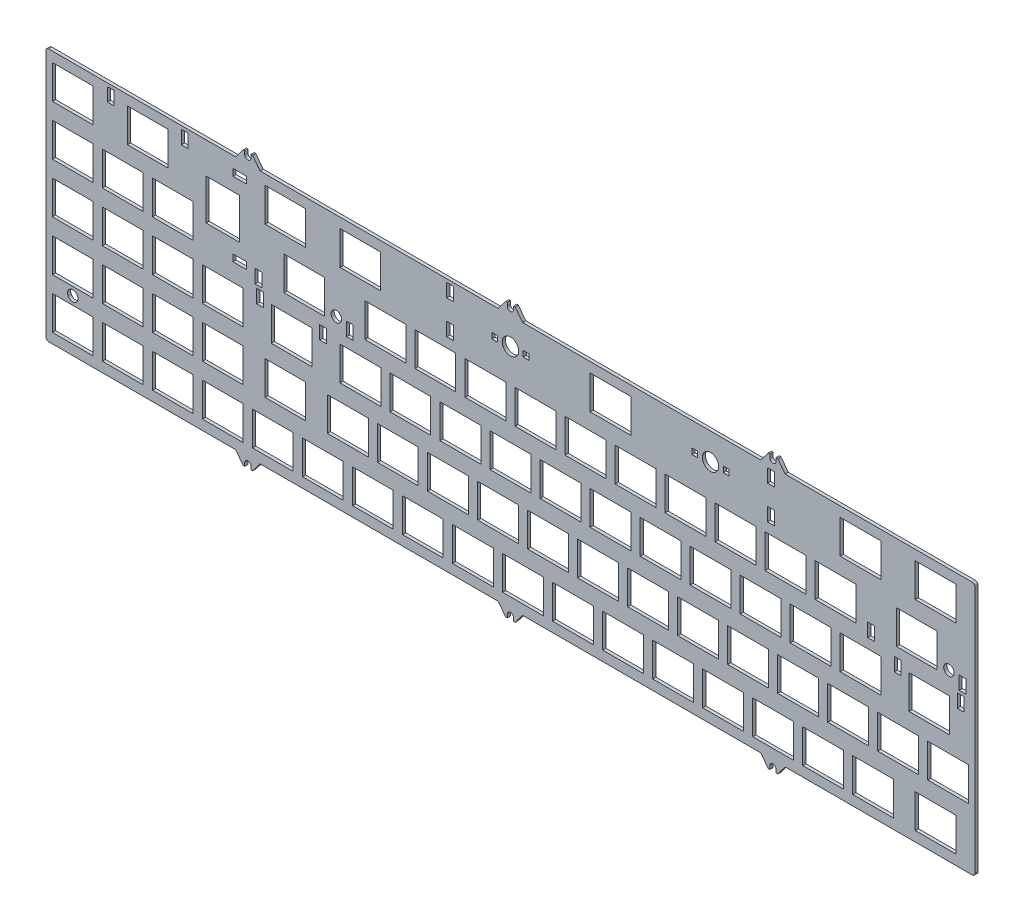
SolidWorks part; units mm, degrees
ref_plane "Front Plane" through (0, 0, 0) normal (0, 0, 1) x (1, 0, 0)
ref_plane "Top Plane" through (0, 0, 0) normal (0, 1, 0) x (1, 0, 0)
ref_plane "Right Plane" through (0, 0, 0) normal (1, 0, 0) x (0, 0, -1)
sketch "Sketch2" plane through (0, 0, 0) normal (0, 0, -1) x (1, 0, 0)
  line L0 (137.0625, 39.4) -> (121.4625, 39.4)
  line L1 (121.4625, 39.4) -> (121.4625, 26.6)
  line L2 (121.4625, 26.6) -> (137.0625, 26.6)
  line L3 (137.0625, 26.6) -> (137.0625, 39.4)
  line L4 (127.5375, 58.45) -> (111.9375, 58.45)
  line L5 (111.9375, 58.45) -> (111.9375, 45.65)
  line L6 (111.9375, 45.65) -> (127.5375, 45.65)
  line L7 (127.5375, 45.65) -> (127.5375, 58.45)
  line L8 (122.775, 77.5) -> (107.175, 77.5)
  line L9 (107.175, 77.5) -> (107.175, 64.7)
  line L10 (107.175, 64.7) -> (122.775, 64.7)
  line L11 (122.775, 64.7) -> (122.775, 77.5)
  line L12 (325.7312, 43.1) -> (325.7312, 48.2)
  line L13 (325.7312, 48.2) -> (323.1312, 48.2)
  line L14 (323.1312, 48.2) -> (323.1312, 43.1)
  line L15 (323.1312, 43.1) -> (325.7312, 43.1)
  line L16 (347.1312, 43.1) -> (347.1312, 48.2)
  line L17 (347.1312, 48.2) -> (349.7312, 48.2)
  line L18 (349.7312, 48.2) -> (349.7312, 43.1)
  line L19 (349.7312, 43.1) -> (347.1312, 43.1)
  line L20 (104.2437, 43.1) -> (104.2437, 48.2)
  line L21 (104.2437, 48.2) -> (106.8437, 48.2)
  line L22 (106.8437, 48.2) -> (106.8437, 43.1)
  line L23 (106.8437, 43.1) -> (104.2437, 43.1)
  line L24 (315.5687, 36.85) -> (315.5687, 41.95)
  line L25 (315.5687, 41.95) -> (312.9687, 41.95)
  line L26 (312.9687, 41.95) -> (312.9687, 36.85)
  line L27 (312.9687, 36.85) -> (315.5687, 36.85)
  line L28 (347.7687, 36.85) -> (347.7687, 41.95)
  line L29 (347.7687, 41.95) -> (350.3687, 41.95)
  line L30 (350.3687, 41.95) -> (350.3687, 36.85)
  line L31 (350.3687, 36.85) -> (347.7687, 36.85)
  line L32 (114.4062, 36.85) -> (114.4062, 41.95)
  line L33 (114.4062, 41.95) -> (117.0062, 41.95)
  line L34 (117.0062, 41.95) -> (117.0062, 36.85)
  line L35 (117.0062, 36.85) -> (114.4062, 36.85)
  line L36 (155.1875, 5) -> (155.1875, 10.1)
  line L37 (155.1875, 10.1) -> (152.5875, 10.1)
  line L38 (152.5875, 10.1) -> (152.5875, 5)
  line L39 (152.5875, 5) -> (155.1875, 5)
  line L40 (183.9625, 15.05) -> (183.9625, 12.85)
  line L41 (183.9625, 12.85) -> (181.7625, 12.85)
  line L42 (181.7625, 12.85) -> (181.7625, 15.05)
  line L43 (181.7625, 15.05) -> (183.9625, 15.05)
  line L44 (169.8125, 12.85) -> (169.8125, 15.05)
  line L45 (169.8125, 15.05) -> (172.0125, 15.05)
  line L46 (172.0125, 15.05) -> (172.0125, 12.85)
  line L47 (172.0125, 12.85) -> (169.8125, 12.85)
  line L48 (246.0125, 15.05) -> (246.0125, 12.85)
  line L49 (246.0125, 12.85) -> (248.2125, 12.85)
  line L50 (248.2125, 12.85) -> (248.2125, 15.05)
  line L51 (248.2125, 15.05) -> (246.0125, 15.05)
  line L52 (260.1625, 12.85) -> (260.1625, 15.05)
  line L53 (260.1625, 15.05) -> (257.9625, 15.05)
  line L54 (257.9625, 15.05) -> (257.9625, 12.85)
  line L55 (257.9625, 12.85) -> (260.1625, 12.85)
  line L56 (82.8437, 43.1) -> (82.8437, 48.2)
  line L57 (82.8437, 48.2) -> (80.2437, 48.2)
  line L58 (80.2437, 48.2) -> (80.2437, 43.1)
  line L59 (80.2437, 43.1) -> (82.8437, 43.1)
  line L60 (82.2062, 36.85) -> (82.2062, 41.95)
  line L61 (82.2062, 41.95) -> (79.6062, 41.95)
  line L62 (79.6062, 41.95) -> (79.6062, 36.85)
  line L63 (79.6062, 36.85) -> (82.2062, 36.85)
  line L64 (25.975, 5) -> (25.975, 10.1)
  line L65 (25.975, 10.1) -> (23.375, 10.1)
  line L66 (23.375, 10.1) -> (23.375, 5)
  line L67 (23.375, 5) -> (25.975, 5)
  line L68 (51.575, 5) -> (51.575, 10.1)
  line L69 (51.575, 10.1) -> (54.175, 10.1)
  line L70 (54.175, 10.1) -> (54.175, 5)
  line L71 (54.175, 5) -> (51.575, 5)
  line L72 (76.3, 10.675) -> (71.2, 10.675)
  line L73 (71.2, 10.675) -> (71.2, 8.075)
  line L74 (71.2, 8.075) -> (76.3, 8.075)
  line L75 (76.3, 8.075) -> (76.3, 10.675)
  line L76 (76.3, 36.275) -> (71.2, 36.275)
  line L77 (71.2, 36.275) -> (71.2, 38.875)
  line L78 (71.2, 38.875) -> (76.3, 38.875)
  line L79 (76.3, 38.875) -> (76.3, 36.275)
  line L80 (155.1875, 22.9) -> (155.1875, 17.8)
  line L81 (155.1875, 17.8) -> (152.5875, 17.8)
  line L82 (152.5875, 17.8) -> (152.5875, 22.9)
  line L83 (152.5875, 22.9) -> (155.1875, 22.9)
  line L84 (277.3875, 22.9) -> (277.3875, 17.8)
  line L85 (277.3875, 17.8) -> (274.7875, 17.8)
  line L86 (274.7875, 17.8) -> (274.7875, 22.9)
  line L87 (274.7875, 22.9) -> (277.3875, 22.9)
  line L88 (274.7875, 5) -> (274.7875, 10.1)
  line L89 (274.7875, 10.1) -> (277.3875, 10.1)
  line L90 (277.3875, 10.1) -> (277.3875, 5)
  line L91 (277.3875, 5) -> (274.7875, 5)
  line L92 (0, 4.75) -> (0, 99.35)
  line L93 (353.775, 4.75) -> (353.775, 99.35)
  line L94 (75.0875, 104.1) -> (72.2375, 100.35)
  line L95 (75.0875, 104.1) -> (75.6875, 104.1)
  line L96 (75.6875, 104.1) -> (75.6875, 103.6)
  line L97 (78.6875, 104.1) -> (81.5375, 100.35)
  line L98 (78.6875, 104.1) -> (78.0875, 104.1)
  line L99 (78.0875, 104.1) -> (78.0875, 103.6)
  line L100 (175.0875, 104.1) -> (172.2375, 100.35)
  line L101 (175.0875, 104.1) -> (175.6875, 104.1)
  line L102 (178.6875, 104.1) -> (181.5375, 100.35)
  line L103 (178.6875, 104.1) -> (178.0875, 104.1)
  line L104 (275.0875, 104.1) -> (272.2375, 100.35)
  line L105 (275.0875, 104.1) -> (275.6875, 104.1)
  line L106 (278.6875, 104.1) -> (281.5375, 100.35)
  line L107 (278.6875, 104.1) -> (278.0875, 104.1)
  line L108 (272.2375, 100.35) -> (181.5375, 100.35)
  line L109 (172.2375, 100.35) -> (81.5375, 100.35)
  line L110 (72.2375, 100.35) -> (1, 100.35)
  line L111 (352.775, 100.35) -> (281.5375, 100.35)
  line L112 (272.2375, 3.75) -> (181.5375, 3.75)
  line L113 (172.2375, 3.75) -> (81.5375, 3.75)
  line L114 (72.2375, 3.75) -> (1, 3.75)
  line L115 (352.775, 3.75) -> (281.5375, 3.75)
  line L116 (331.0625, 83.75) -> (346.5625, 83.75)
  line L117 (346.5625, 83.75) -> (346.5625, 96.55)
  line L118 (346.5625, 96.55) -> (331.0625, 96.55)
  line L119 (331.0625, 96.55) -> (331.0625, 83.75)
  line L120 (307.25, 83.75) -> (322.75, 83.75)
  line L121 (322.75, 83.75) -> (322.75, 96.55)
  line L122 (322.75, 96.55) -> (307.25, 96.55)
  line L123 (307.25, 96.55) -> (307.25, 83.75)
  line L124 (288.2, 83.75) -> (303.7, 83.75)
  line L125 (303.7, 83.75) -> (303.7, 96.55)
  line L126 (303.7, 96.55) -> (288.2, 96.55)
  line L127 (288.2, 96.55) -> (288.2, 83.75)
  line L128 (269.15, 83.75) -> (284.65, 83.75)
  line L129 (284.65, 83.75) -> (284.65, 96.55)
  line L130 (284.65, 96.55) -> (269.15, 96.55)
  line L131 (269.15, 96.55) -> (269.15, 83.75)
  line L132 (250.1, 83.75) -> (265.6, 83.75)
  line L133 (265.6, 83.75) -> (265.6, 96.55)
  line L134 (265.6, 96.55) -> (250.1, 96.55)
  line L135 (250.1, 96.55) -> (250.1, 83.75)
  line L136 (231.05, 83.75) -> (246.55, 83.75)
  line L137 (246.55, 83.75) -> (246.55, 96.55)
  line L138 (246.55, 96.55) -> (231.05, 96.55)
  line L139 (231.05, 96.55) -> (231.05, 83.75)
  line L140 (212, 83.75) -> (227.5, 83.75)
  line L141 (227.5, 83.75) -> (227.5, 96.55)
  line L142 (227.5, 96.55) -> (212, 96.55)
  line L143 (212, 96.55) -> (212, 83.75)
  line L144 (192.95, 83.75) -> (208.45, 83.75)
  line L145 (208.45, 83.75) -> (208.45, 96.55)
  line L146 (208.45, 96.55) -> (192.95, 96.55)
  line L147 (192.95, 96.55) -> (192.95, 83.75)
  line L148 (173.9, 83.75) -> (189.4, 83.75)
  line L149 (189.4, 83.75) -> (189.4, 96.55)
  line L150 (189.4, 96.55) -> (173.9, 96.55)
  line L151 (173.9, 96.55) -> (173.9, 83.75)
  line L152 (154.85, 83.75) -> (170.35, 83.75)
  line L153 (170.35, 83.75) -> (170.35, 96.55)
  line L154 (170.35, 96.55) -> (154.85, 96.55)
  line L155 (154.85, 96.55) -> (154.85, 83.75)
  line L156 (135.8, 83.75) -> (151.3, 83.75)
  line L157 (151.3, 83.75) -> (151.3, 96.55)
  line L158 (151.3, 96.55) -> (135.8, 96.55)
  line L159 (135.8, 96.55) -> (135.8, 83.75)
  line L160 (116.75, 83.75) -> (132.25, 83.75)
  line L161 (132.25, 83.75) -> (132.25, 96.55)
  line L162 (132.25, 96.55) -> (116.75, 96.55)
  line L163 (116.75, 96.55) -> (116.75, 83.75)
  line L164 (97.7, 83.75) -> (113.2, 83.75)
  line L165 (113.2, 83.75) -> (113.2, 96.55)
  line L166 (113.2, 96.55) -> (97.7, 96.55)
  line L167 (97.7, 96.55) -> (97.7, 83.75)
  line L168 (78.65, 83.75) -> (94.15, 83.75)
  line L169 (94.15, 83.75) -> (94.15, 96.55)
  line L170 (94.15, 96.55) -> (78.65, 96.55)
  line L171 (78.65, 96.55) -> (78.65, 83.75)
  line L172 (59.6, 77.5) -> (75.1, 77.5)
  line L173 (75.1, 64.7) -> (75.1, 77.5)
  line L174 (75.1, 96.55) -> (59.6, 96.55)
  line L175 (59.6, 77.5) -> (59.6, 64.7)
  line L176 (40.55, 77.5) -> (56.05, 77.5)
  line L177 (56.05, 64.7) -> (56.05, 77.5)
  line L178 (56.05, 96.55) -> (40.55, 96.55)
  line L179 (40.55, 77.5) -> (40.55, 64.7)
  line L180 (21.5, 77.5) -> (37, 77.5)
  line L181 (37, 64.7) -> (37, 77.5)
  line L182 (37, 96.55) -> (21.5, 96.55)
  line L183 (21.5, 77.5) -> (21.5, 64.7)
  line L184 (2.45, 77.5) -> (17.95, 77.5)
  line L185 (17.95, 64.7) -> (17.95, 77.5)
  line L186 (17.95, 96.55) -> (2.45, 96.55)
  line L187 (2.45, 77.5) -> (2.45, 64.7)
  line L188 (59.6, 64.7) -> (75.1, 64.7)
  line L189 (75.1, 83.75) -> (75.1, 96.55)
  line L190 (75.1, 83.75) -> (59.6, 83.75)
  line L191 (59.6, 96.55) -> (59.6, 83.75)
  line L192 (40.55, 64.7) -> (56.05, 64.7)
  line L193 (56.05, 83.75) -> (56.05, 96.55)
  line L194 (56.05, 83.75) -> (40.55, 83.75)
  line L195 (40.55, 96.55) -> (40.55, 83.75)
  line L196 (21.5, 64.7) -> (37, 64.7)
  line L197 (37, 83.75) -> (37, 96.55)
  line L198 (37, 83.75) -> (21.5, 83.75)
  line L199 (21.5, 96.55) -> (21.5, 83.75)
  line L200 (2.45, 64.7) -> (17.95, 64.7)
  line L201 (17.95, 83.75) -> (17.95, 96.55)
  line L202 (17.95, 83.75) -> (2.45, 83.75)
  line L203 (2.45, 96.55) -> (2.45, 83.75)
  line L204 (59.55, 45.65) -> (75.05, 45.65)
  line L205 (75.05, 45.65) -> (75.05, 58.45)
  line L206 (75.05, 58.45) -> (59.55, 58.45)
  line L207 (59.55, 58.45) -> (59.55, 45.65)
  line L208 (40.5, 45.65) -> (56, 45.65)
  line L209 (56, 45.65) -> (56, 58.45)
  line L210 (56, 58.45) -> (40.5, 58.45)
  line L211 (40.5, 58.45) -> (40.5, 45.65)
  line L212 (21.45, 45.65) -> (36.95, 45.65)
  line L213 (36.95, 45.65) -> (36.95, 58.45)
  line L214 (36.95, 58.45) -> (21.45, 58.45)
  line L215 (21.45, 58.45) -> (21.45, 45.65)
  line L216 (2.4, 45.65) -> (17.9, 45.65)
  line L217 (17.9, 45.65) -> (17.9, 58.45)
  line L218 (17.9, 58.45) -> (2.4, 58.45)
  line L219 (2.4, 58.45) -> (2.4, 45.65)
  line L220 (40.5, 26.6) -> (56, 26.6)
  line L221 (56, 26.6) -> (56, 39.4)
  line L222 (56, 39.4) -> (40.5, 39.4)
  line L223 (40.5, 39.4) -> (40.5, 26.6)
  line L224 (21.45, 26.6) -> (36.95, 26.6)
  line L225 (36.95, 26.6) -> (36.95, 39.4)
  line L226 (36.95, 39.4) -> (21.45, 39.4)
  line L227 (21.45, 39.4) -> (21.45, 26.6)
  line L228 (2.4, 26.6) -> (17.9, 26.6)
  line L229 (17.9, 26.6) -> (17.9, 39.4)
  line L230 (17.9, 39.4) -> (2.4, 39.4)
  line L231 (2.4, 39.4) -> (2.4, 26.6)
  line L232 (2.45, 7.55) -> (17.95, 7.55)
  line L233 (17.95, 7.55) -> (17.95, 20.35)
  line L234 (17.95, 20.35) -> (2.45, 20.35)
  line L235 (2.45, 20.35) -> (2.45, 7.55)
  line L236 (31.025, 7.55) -> (46.525, 7.55)
  line L237 (46.525, 7.55) -> (46.525, 20.35)
  line L238 (46.525, 20.35) -> (31.025, 20.35)
  line L239 (31.025, 20.35) -> (31.025, 7.55)
  line L240 (83.4125, 7.55) -> (98.9125, 7.55)
  line L241 (98.9125, 7.55) -> (98.9125, 20.35)
  line L242 (98.9125, 20.35) -> (83.4125, 20.35)
  line L243 (83.4125, 20.35) -> (83.4125, 7.55)
  line L244 (111.9875, 7.55) -> (127.4875, 7.55)
  line L245 (127.4875, 7.55) -> (127.4875, 20.35)
  line L246 (127.4875, 20.35) -> (111.9875, 20.35)
  line L247 (111.9875, 20.35) -> (111.9875, 7.55)
  line L248 (90.5562, 26.6) -> (106.0562, 26.6)
  line L249 (106.0562, 26.6) -> (106.0562, 39.4)
  line L250 (106.0562, 39.4) -> (90.5562, 39.4)
  line L251 (90.5562, 39.4) -> (90.5562, 26.6)
  line L252 (85.7937, 45.65) -> (101.2937, 45.65)
  line L253 (101.2937, 45.65) -> (101.2937, 58.45)
  line L254 (101.2937, 58.45) -> (85.7937, 58.45)
  line L255 (85.7937, 58.45) -> (85.7937, 45.65)
  line L256 (83.4125, 64.7) -> (98.9125, 64.7)
  line L257 (98.9125, 64.7) -> (98.9125, 77.5)
  line L258 (98.9125, 77.5) -> (83.4125, 77.5)
  line L259 (83.4125, 77.5) -> (83.4125, 64.7)
  line L260 (328.6812, 45.65) -> (344.1812, 45.65)
  line L261 (344.1812, 45.65) -> (344.1812, 58.45)
  line L262 (344.1812, 58.45) -> (328.6812, 58.45)
  line L263 (328.6812, 58.45) -> (328.6812, 45.65)
  line L264 (207.2375, 7.55) -> (222.7375, 7.55)
  line L265 (222.7375, 7.55) -> (222.7375, 20.35)
  line L266 (222.7375, 20.35) -> (207.2375, 20.35)
  line L267 (207.2375, 20.35) -> (207.2375, 7.55)
  line L268 (302.4875, 7.55) -> (317.9875, 7.55)
  line L269 (317.9875, 7.55) -> (317.9875, 20.35)
  line L270 (317.9875, 20.35) -> (302.4875, 20.35)
  line L271 (302.4875, 20.35) -> (302.4875, 7.55)
  line L272 (323.9187, 26.6) -> (339.4187, 26.6)
  line L273 (339.4187, 26.6) -> (339.4187, 39.4)
  line L274 (339.4187, 39.4) -> (323.9187, 39.4)
  line L275 (323.9187, 39.4) -> (323.9187, 26.6)
  line L276 (331.0625, 7.55) -> (346.5625, 7.55)
  line L277 (346.5625, 7.55) -> (346.5625, 20.35)
  line L278 (346.5625, 20.35) -> (331.0625, 20.35)
  line L279 (331.0625, 20.35) -> (331.0625, 7.55)
  line L280 (73.75, 15.725) -> (73.75, 31.225)
  line L281 (73.75, 31.225) -> (60.95, 31.225)
  line L282 (60.95, 31.225) -> (60.95, 15.725)
  line L283 (60.95, 15.725) -> (73.75, 15.725)
  line L284 (278.675, 64.7) -> (294.175, 64.7)
  line L285 (294.175, 64.7) -> (294.175, 77.5)
  line L286 (294.175, 77.5) -> (278.675, 77.5)
  line L287 (278.675, 77.5) -> (278.675, 64.7)
  line L288 (259.625, 64.7) -> (275.125, 64.7)
  line L289 (275.125, 64.7) -> (275.125, 77.5)
  line L290 (275.125, 77.5) -> (259.625, 77.5)
  line L291 (259.625, 77.5) -> (259.625, 64.7)
  line L292 (240.575, 64.7) -> (256.075, 64.7)
  line L293 (256.075, 64.7) -> (256.075, 77.5)
  line L294 (256.075, 77.5) -> (240.575, 77.5)
  line L295 (240.575, 77.5) -> (240.575, 64.7)
  line L296 (221.525, 64.7) -> (237.025, 64.7)
  line L297 (237.025, 64.7) -> (237.025, 77.5)
  line L298 (237.025, 77.5) -> (221.525, 77.5)
  line L299 (221.525, 77.5) -> (221.525, 64.7)
  line L300 (202.475, 64.7) -> (217.975, 64.7)
  line L301 (217.975, 64.7) -> (217.975, 77.5)
  line L302 (217.975, 77.5) -> (202.475, 77.5)
  line L303 (202.475, 77.5) -> (202.475, 64.7)
  line L304 (183.425, 64.7) -> (198.925, 64.7)
  line L305 (198.925, 64.7) -> (198.925, 77.5)
  line L306 (198.925, 77.5) -> (183.425, 77.5)
  line L307 (183.425, 77.5) -> (183.425, 64.7)
  line L308 (164.375, 64.7) -> (179.875, 64.7)
  line L309 (179.875, 64.7) -> (179.875, 77.5)
  line L310 (179.875, 77.5) -> (164.375, 77.5)
  line L311 (164.375, 77.5) -> (164.375, 64.7)
  line L312 (145.325, 64.7) -> (160.825, 64.7)
  line L313 (160.825, 64.7) -> (160.825, 77.5)
  line L314 (160.825, 77.5) -> (145.325, 77.5)
  line L315 (145.325, 77.5) -> (145.325, 64.7)
  line L316 (126.275, 64.7) -> (141.775, 64.7)
  line L317 (141.775, 64.7) -> (141.775, 77.5)
  line L318 (141.775, 77.5) -> (126.275, 77.5)
  line L319 (126.275, 77.5) -> (126.275, 64.7)
  line L320 (283.4375, 45.65) -> (298.9375, 45.65)
  line L321 (298.9375, 45.65) -> (298.9375, 58.45)
  line L322 (298.9375, 58.45) -> (283.4375, 58.45)
  line L323 (283.4375, 58.45) -> (283.4375, 45.65)
  line L324 (264.3875, 45.65) -> (279.8875, 45.65)
  line L325 (279.8875, 45.65) -> (279.8875, 58.45)
  line L326 (279.8875, 58.45) -> (264.3875, 58.45)
  line L327 (264.3875, 58.45) -> (264.3875, 45.65)
  line L328 (245.3375, 45.65) -> (260.8375, 45.65)
  line L329 (260.8375, 45.65) -> (260.8375, 58.45)
  line L330 (260.8375, 58.45) -> (245.3375, 58.45)
  line L331 (245.3375, 58.45) -> (245.3375, 45.65)
  line L332 (226.2875, 45.65) -> (241.7875, 45.65)
  line L333 (241.7875, 45.65) -> (241.7875, 58.45)
  line L334 (241.7875, 58.45) -> (226.2875, 58.45)
  line L335 (226.2875, 58.45) -> (226.2875, 45.65)
  line L336 (207.2375, 45.65) -> (222.7375, 45.65)
  line L337 (222.7375, 45.65) -> (222.7375, 58.45)
  line L338 (222.7375, 58.45) -> (207.2375, 58.45)
  line L339 (207.2375, 58.45) -> (207.2375, 45.65)
  line L340 (188.1875, 45.65) -> (203.6875, 45.65)
  line L341 (203.6875, 45.65) -> (203.6875, 58.45)
  line L342 (203.6875, 58.45) -> (188.1875, 58.45)
  line L343 (188.1875, 58.45) -> (188.1875, 45.65)
  line L344 (169.1375, 45.65) -> (184.6375, 45.65)
  line L345 (184.6375, 45.65) -> (184.6375, 58.45)
  line L346 (184.6375, 58.45) -> (169.1375, 58.45)
  line L347 (169.1375, 58.45) -> (169.1375, 45.65)
  line L348 (150.0875, 45.65) -> (165.5875, 45.65)
  line L349 (165.5875, 45.65) -> (165.5875, 58.45)
  line L350 (165.5875, 58.45) -> (150.0875, 58.45)
  line L351 (150.0875, 58.45) -> (150.0875, 45.65)
  line L352 (131.0375, 45.65) -> (146.5375, 45.65)
  line L353 (146.5375, 45.65) -> (146.5375, 58.45)
  line L354 (146.5375, 58.45) -> (131.0375, 58.45)
  line L355 (131.0375, 58.45) -> (131.0375, 45.65)
  line L356 (292.9625, 26.6) -> (308.4625, 26.6)
  line L357 (308.4625, 26.6) -> (308.4625, 39.4)
  line L358 (308.4625, 39.4) -> (292.9625, 39.4)
  line L359 (292.9625, 39.4) -> (292.9625, 26.6)
  line L360 (273.9125, 26.6) -> (289.4125, 26.6)
  line L361 (289.4125, 26.6) -> (289.4125, 39.4)
  line L362 (289.4125, 39.4) -> (273.9125, 39.4)
  line L363 (273.9125, 39.4) -> (273.9125, 26.6)
  line L364 (254.8625, 26.6) -> (270.3625, 26.6)
  line L365 (270.3625, 26.6) -> (270.3625, 39.4)
  line L366 (270.3625, 39.4) -> (254.8625, 39.4)
  line L367 (254.8625, 39.4) -> (254.8625, 26.6)
  line L368 (235.8125, 26.6) -> (251.3125, 26.6)
  line L369 (251.3125, 26.6) -> (251.3125, 39.4)
  line L370 (251.3125, 39.4) -> (235.8125, 39.4)
  line L371 (235.8125, 39.4) -> (235.8125, 26.6)
  line L372 (216.7625, 26.6) -> (232.2625, 26.6)
  line L373 (232.2625, 26.6) -> (232.2625, 39.4)
  line L374 (232.2625, 39.4) -> (216.7625, 39.4)
  line L375 (216.7625, 39.4) -> (216.7625, 26.6)
  line L376 (197.7125, 26.6) -> (213.2125, 26.6)
  line L377 (213.2125, 26.6) -> (213.2125, 39.4)
  line L378 (213.2125, 39.4) -> (197.7125, 39.4)
  line L379 (197.7125, 39.4) -> (197.7125, 26.6)
  line L380 (178.6625, 26.6) -> (194.1625, 26.6)
  line L381 (194.1625, 26.6) -> (194.1625, 39.4)
  line L382 (194.1625, 39.4) -> (178.6625, 39.4)
  line L383 (178.6625, 39.4) -> (178.6625, 26.6)
  line L384 (159.6125, 26.6) -> (175.1125, 26.6)
  line L385 (175.1125, 26.6) -> (175.1125, 39.4)
  line L386 (175.1125, 39.4) -> (159.6125, 39.4)
  line L387 (159.6125, 39.4) -> (159.6125, 26.6)
  line L388 (140.5625, 26.6) -> (156.0625, 26.6)
  line L389 (156.0625, 26.6) -> (156.0625, 39.4)
  line L390 (156.0625, 39.4) -> (140.5625, 39.4)
  line L391 (140.5625, 39.4) -> (140.5625, 26.6)
  line L392 (335.825, 64.7) -> (351.325, 64.7)
  line L393 (351.325, 64.7) -> (351.325, 77.5)
  line L394 (351.325, 77.5) -> (335.825, 77.5)
  line L395 (335.825, 77.5) -> (335.825, 64.7)
  line L396 (316.775, 64.7) -> (332.275, 64.7)
  line L397 (332.275, 64.7) -> (332.275, 77.5)
  line L398 (332.275, 77.5) -> (316.775, 77.5)
  line L399 (316.775, 77.5) -> (316.775, 64.7)
  line L400 (297.725, 64.7) -> (313.225, 64.7)
  line L401 (313.225, 64.7) -> (313.225, 77.5)
  line L402 (313.225, 77.5) -> (297.725, 77.5)
  line L403 (297.725, 77.5) -> (297.725, 64.7)
  line L404 (302.4875, 45.65) -> (317.9875, 45.65)
  line L405 (317.9875, 45.65) -> (317.9875, 58.45)
  line L406 (317.9875, 58.45) -> (302.4875, 58.45)
  line L407 (302.4875, 58.45) -> (302.4875, 45.65)
  line L408 (278.0875, 102.85) -> (278.0875, 104.1)
  line L409 (275.6875, 102.85) -> (275.6875, 104.1)
  line L410 (178.0875, 102.85) -> (178.0875, 104.1)
  line L411 (175.6875, 102.85) -> (175.6875, 104.1)
  line L412 (78.0875, 102.85) -> (78.0875, 103.6)
  line L413 (75.6875, 102.85) -> (75.6875, 103.6)
  line L414 (75.0875, 0) -> (72.2375, 3.75)
  line L415 (75.0875, 0) -> (75.6875, 0)
  line L416 (75.6875, 0) -> (75.6875, 0.5)
  line L417 (78.6875, 0) -> (81.5375, 3.75)
  line L418 (78.6875, 0) -> (78.0875, 0)
  line L419 (78.0875, 0) -> (78.0875, 0.5)
  line L420 (175.0875, 0) -> (172.2375, 3.75)
  line L421 (175.0875, 0) -> (175.6875, 0)
  line L422 (178.6875, 0) -> (181.5375, 3.75)
  line L423 (178.6875, 0) -> (178.0875, 0)
  line L424 (275.0875, 0) -> (272.2375, 3.75)
  line L425 (275.0875, 0) -> (275.6875, 0)
  line L426 (278.6875, 0) -> (281.5375, 3.75)
  line L427 (278.6875, 0) -> (278.0875, 0)
  line L428 (278.0875, 1.25) -> (278.0875, 0)
  line L429 (275.6875, 1.25) -> (275.6875, 0)
  line L430 (178.0875, 1.25) -> (178.0875, 0)
  line L431 (175.6875, 1.25) -> (175.6875, 0)
  line L432 (78.0875, 1.25) -> (78.0875, 0.5)
  line L433 (75.6875, 1.25) -> (75.6875, 0.5)
  circle A0 centre (176.8875, 13.95) radius 3.125
  circle A1 centre (253.0875, 13.95) radius 3.125
  arc A2 (0, 4.75) -> (1, 3.75) centre (1, 4.75) ccw
  arc A3 (1, 100.35) -> (0, 99.35) centre (1, 99.35) ccw
  arc A4 (75.6875, 102.85) -> (78.0875, 102.85) centre (76.8875, 102.85) ccw
  arc A5 (175.6875, 102.85) -> (178.0875, 102.85) centre (176.8875, 102.85) ccw
  arc A6 (275.6875, 102.85) -> (278.0875, 102.85) centre (276.8875, 102.85) ccw
  arc A7 (352.775, 3.75) -> (353.775, 4.75) centre (352.775, 4.75) ccw
  arc A8 (353.775, 99.35) -> (352.775, 100.35) centre (352.775, 99.35) ccw
  circle A9 centre (343.9187, 37.25) radius 2
  circle A10 centre (110.5562, 37.25) radius 2
  circle A11 centre (10.2, 80.625) radius 2
  arc A12 (78.0875, 1.25) -> (75.6875, 1.25) centre (76.8875, 1.25) ccw
  arc A13 (178.0875, 1.25) -> (175.6875, 1.25) centre (176.8875, 1.25) ccw
  arc A14 (278.0875, 1.25) -> (275.6875, 1.25) centre (276.8875, 1.25) ccw
extrude "Boss-Extrude1" add sketch "Sketch2" against normal blind 1.2
